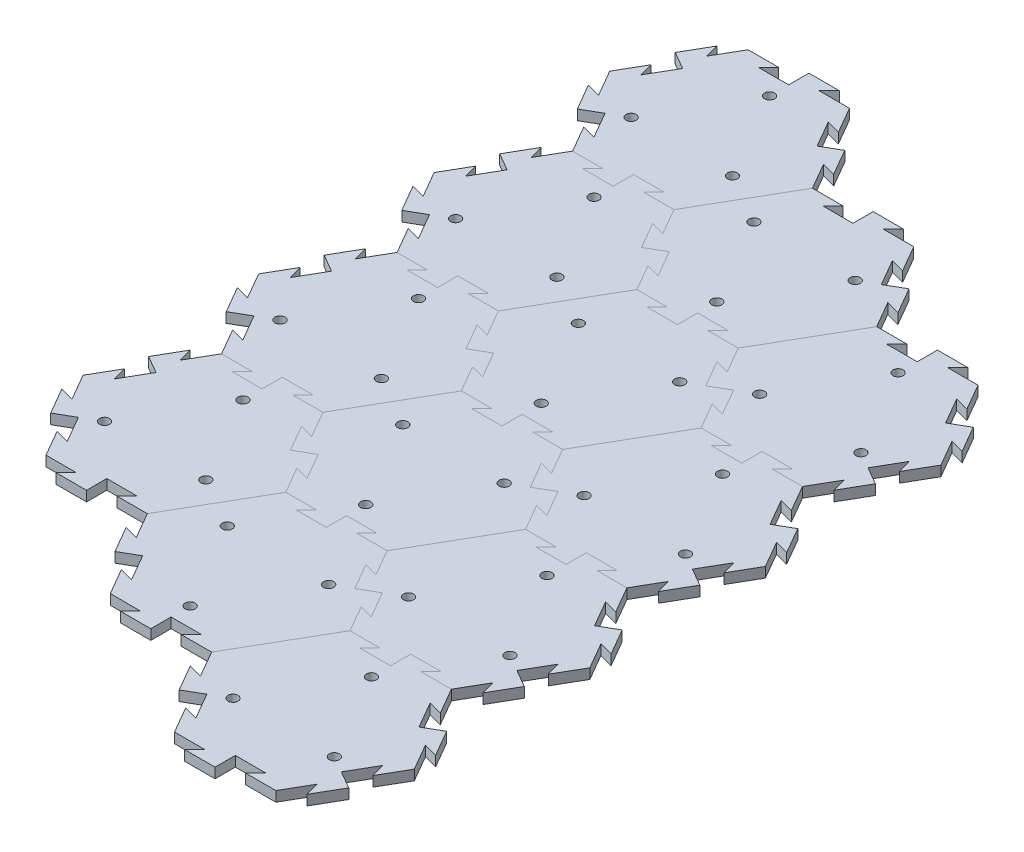
SolidWorks part; units mm, degrees
note: '?' marks a value the reader was unsure of.
material "Cedar"
ref_plane "Front Plane" through (0, 0, 0) normal (0, 0, 1) x (1, 0, 0)
ref_plane "Top Plane" through (0, 0, 0) normal (0, 1, 0) x (1, 0, 0)
ref_plane "Right Plane" through (0, 0, 0) normal (1, 0, 0) x (0, 0, -1)
sketch "Sketch1" plane through (0, 0, 0) normal (0, 1, 0) x (1, 0, 0)
  line L0 (0, 0) -> (63.5, 0) construction
  line L1 (63.5, 0) -> (31.75, 54.9926)
  line L2 (31.75, 54.9926) -> (-31.75, 54.9926)
  line L3 (-31.75, 54.9926) -> (-63.5, 0)
  line L4 (-63.5, 0) -> (-31.75, -54.9926)
  line L5 (-31.75, -54.9926) -> (31.75, -54.9926)
  line L6 (31.75, -54.9926) -> (63.5, 0)
  circle A0 centre (0, 0) radius 54.9926 construction
  dimension "D1" = 63.5
extrude "Boss-Extrude1" add sketch "Sketch1" against normal blind 6.35
sketch "Sketch2" plane through (0, 0, 0) normal (0, 1, 0) x (1, 0, 0)
  point P1 (0, 0)
ref_axis "Axis1" through (0, 0, 0) along (0, 1, 0)?
sketch "Sketch9" plane through (0, 0, 0) normal (0, 1, 0) x (1, 0, 0)
  line L1 (31.75, -18.3309) -> (0, 36.6617) construction
  line L2 (0, 36.6617) -> (-31.75, -18.3309) construction
  line L3 (-31.75, -18.3309) -> (31.75, -18.3309) construction
  circle A0 centre (0, 0) radius 18.3309 construction
  circle A1 centre (-31.75, -18.3309) radius 3.175
  dimension "D2" = 6.35
  dimension "D1" = 63.5
extrude "Cut-Extrude3" cut sketch "Sketch9" against normal through all
pattern_circular "CirPattern6" count 3 over 360 about axis through (0, 0, 0) along (0, 1, 0) of "Cut-Extrude3"
mirror "Mirror3" about plane through (31.75, -6.35, 54.9926) normal (0.866, 0, 0.5) of bodies 121 125
sketch "Sketch10" plane through (0, 0, 0) normal (0, 1, 0) x (1, 0, 0)
  line L0 (31.75, 54.9926) -> (41.275, 38.4948) construction
  line L1 (41.275, 38.4948) -> (32.6007, 40.8191)
  line L2 (32.6007, 40.8191) -> (42.1257, 24.3213)
  line L3 (42.1257, 24.3213) -> (47.625, 27.4963)
  line L4 (41.275, 38.4948) -> (47.625, 27.4963)
  line L5 (63.5, 0) -> (31.75, 54.9926) construction
  dimension "D1" = 45
  dimension "D2" = 6.35
extrude "Cut-Extrude4" cut sketch "Sketch10" against normal through all
sketch "Sketch11" plane through (0, 0, 0) normal (0, 1, 0) x (1, 0, 0)
  line L0 (47.625, 27.4963) -> (63.5, 0) construction
  line L1 (47.625, 27.4963) -> (53.1243, 30.6713)
  line L2 (53.1243, 30.6713) -> (62.6493, 14.1735)
  line L3 (62.6493, 14.1735) -> (53.975, 16.4978)
  line L4 (53.975, 16.4978) -> (47.625, 27.4963)
  line L5 (53.975, 16.4978) -> (63.5, 0) construction
  line L6 (53.975, 16.4978) -> (63.5, 0) construction
  line L7 (63.5, 0) -> (47.625, 27.4963) construction
  line L8 (31.75, -54.9926) -> (63.5, 0) construction
  dimension "D1" = 45
  dimension "D2" = 6.35
extrude "Boss-Extrude4" add sketch "Sketch11" against normal blind 6.35 contours L1 L2 L3 L4
pattern_circular "CirPattern7" count 6 over 360 about axis through (0, 0, 0) along (0, 1, 0) skipping 5 of "Cut-Extrude4", "Boss-Extrude4"
mirror "Mirror4" about plane through (158.75, -6.35, 54.9926) normal (0.866, 0, 0.5) of bodies 126 129
sketch "Sketch12" plane through (0, 0, 0) normal (0, 1, 0) x (1, 0, 0)
  line L0 (127, 0) -> (63.5, -109.9852) construction
  point P4 (95.25, -54.9926)
ref_axis "Axis2" through (95.25, 0, 54.9926) along (0, 1, 0)?
sketch "Sketch13" plane through (0, 0, 0) normal (0, 1, 0) x (1, 0, 0)
  line L0 (127, 0) -> (136.525, -16.4978) construction
  line L1 (136.525, -16.4978) -> (127.8507, -14.1735)
  line L2 (127.8507, -14.1735) -> (137.3757, -30.6713)
  line L3 (137.3757, -30.6713) -> (142.875, -27.4963)
  line L4 (136.525, -16.4978) -> (142.875, -27.4963)
  line L5 (127, 0) -> (158.75, -54.9926) construction
  dimension "D1" = 45
  dimension "D2" = 6.35
extrude "Cut-Extrude5" cut sketch "Sketch13" against normal through all
sketch "Sketch14" plane through (0, 0, 0) normal (0, 1, 0) x (1, 0, 0)
  line L0 (142.875, -27.4963) -> (158.75, -54.9926) construction
  line L1 (142.875, -27.4963) -> (148.3743, -24.3213)
  line L2 (148.3743, -24.3213) -> (157.8993, -40.8191)
  line L3 (157.8993, -40.8191) -> (149.225, -38.4948)
  line L4 (149.225, -38.4948) -> (142.875, -27.4963)
  line L5 (149.225, -38.4948) -> (158.75, -54.9926) construction
  line L6 (149.225, -38.4948) -> (158.75, -54.9926) construction
  dimension "D1" = 45
  dimension "D2" = 6.35
extrude "Boss-Extrude5" add sketch "Sketch14" against normal blind 6.35
pattern_circular "CirPattern8" count 6 over 360 about axis through (95.25, 0, 54.9926) along (0, 1, 0) skipping 2, 5 of "Cut-Extrude5", "Boss-Extrude5"
sketch "Sketch15" plane through (0, 0, 0) normal (0, 1, 0) x (1, 0, 0)
  line L0 (222.25, -54.9926) -> (158.75, -164.9778) construction
  point P4 (190.5, -109.9852)
ref_axis "Axis3" through (190.5, 0, 109.9852) along (0, 1, 0)?
sketch "Sketch16" plane through (0, 0, 0) normal (0, 1, 0) x (1, 0, 0)
  line L0 (222.25, -54.9926) -> (231.775, -71.4904) construction
  line L1 (231.775, -71.4904) -> (223.1007, -69.1661)
  line L2 (223.1007, -69.1661) -> (232.6257, -85.6639)
  line L3 (232.6257, -85.6639) -> (238.125, -82.4889)
  line L4 (231.775, -71.4904) -> (238.125, -82.4889)
  line L5 (254, -109.9852) -> (222.25, -54.9926) construction
  dimension "D1" = 45
  dimension "D2" = 6.35
extrude "Cut-Extrude6" cut sketch "Sketch16" against normal through all
sketch "Sketch17" plane through (0, 0, 0) normal (0, 1, 0) x (1, 0, 0)
  line L0 (238.125, -82.4889) -> (254, -109.9852) construction
  line L1 (238.125, -82.4889) -> (243.6243, -79.3139)
  line L2 (243.6243, -79.3139) -> (253.1493, -95.8117)
  line L3 (253.1493, -95.8117) -> (244.475, -93.4874)
  line L4 (244.475, -93.4874) -> (238.125, -82.4889)
  line L5 (244.475, -93.4874) -> (254, -109.9852) construction
  line L6 (244.475, -93.4874) -> (254, -109.9852) construction
  line L7 (254, -109.9852) -> (238.125, -82.4889) construction
  dimension "D1" = 6.35
  dimension "D2" = 45
extrude "Boss-Extrude6" add sketch "Sketch17" against normal up to surface (6.35 mm away) up to face at (224.9996, -6.35, 126.7286)
pattern_circular "CirPattern9" count 6 over 360 about axis through (190.5, 0, 109.9852) along (0, 1, 0) skipping 2 of "Cut-Extrude6", "Boss-Extrude6"
pattern_linear "LPattern1" count 4 spacing 109.9852 along (0, 0, -1) of bodies 125 133 129
